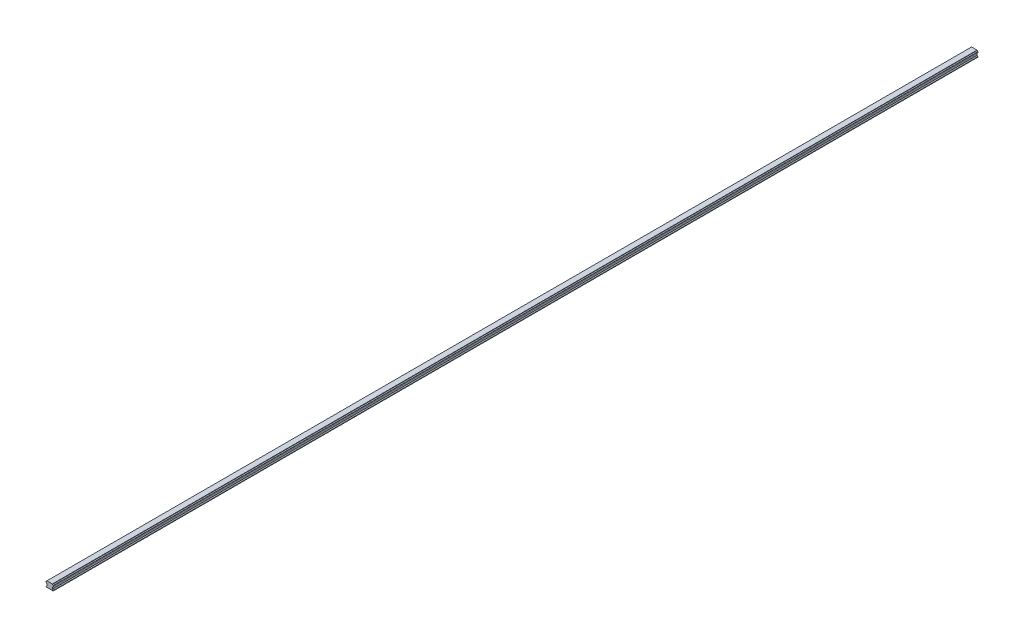
SolidWorks part; units mm, degrees
ref_plane "Piano frontale" through (0, 0, 0) normal (0, 0, 1) x (1, 0, 0)
ref_plane "Piano superiore" through (0, 0, 0) normal (0, 1, 0) x (1, 0, 0)
ref_plane "Piano destro" through (0, 0, 0) normal (1, 0, 0) x (0, 0, -1)
sketch "Schizzo1" plane through (0, 0, 0) normal (0, 0, 1) x (1, 0, 0)
  line L0 (-10.0871, -16.416) -> (-7.5656, -13.8945)
  line L1 (-7.5656, -13.8945) -> (-7.5656, -8.8516)
  line L2 (-7.5656, -8.8516) -> (-8.0776, -8.3396)
  line L3 (-10.3951, -6.0221) -> (-10.5914, -5.8258)
  line L4 (-10.5914, -5.8258) -> (-10.5914, -2.8001)
  line L5 (-10.5914, -2.8001) -> (-10.3951, -2.6038)
  line L6 (-8.0776, -0.2862) -> (-7.5656, 0.2257)
  line L7 (-7.5656, 0.2257) -> (9.5804, 0.2257)
  line L8 (9.5804, 0.2257) -> (10.0923, -0.2862)
  line L9 (12.4099, -2.6038) -> (12.6061, -2.8001)
  line L10 (12.6061, -2.8001) -> (12.6061, -5.8258)
  line L11 (12.6061, -5.8258) -> (12.4099, -6.0221)
  line L12 (10.0923, -8.3396) -> (9.5804, -8.8516)
  line L13 (9.5804, -8.8516) -> (9.5804, -13.8945)
  line L14 (9.5804, -13.8945) -> (12.1018, -16.416)
  line L16 (-10.0871, -16.416) -> (-10.0871, -17.7743)
  line L17 (-10.0871, -17.7743) -> (12.1018, -17.7743)
  line L18 (12.1018, -17.7743) -> (12.1018, -16.416)
  arc A0 (-8.0776, -8.3396) -> (-10.3951, -6.0221) centre (-10.5914, -8.5359) ccw
  arc A1 (-10.3951, -2.6038) -> (-8.0776, -0.2862) centre (-10.5914, -0.09) ccw
  arc A2 (10.0923, -0.2862) -> (12.4099, -2.6038) centre (12.6061, -0.09) ccw
  arc A3 (12.4099, -6.0221) -> (10.0923, -8.3396) centre (12.6061, -8.5359) ccw
  dimension "D1" = 18
extrude "Estrusione-Estrusione1" add sketch "Schizzo1" along direction (0, 0, 1) on the side of the normal blind 2897 from surface contours A3 L11 L10 L9 A2 L8 L7 L6 A1 L5 L4 L3 A0 L2 L1 L0 L14 L13 L12 region at (1.0074, -8.6641, 0) starting at plane "Piano frontale"
